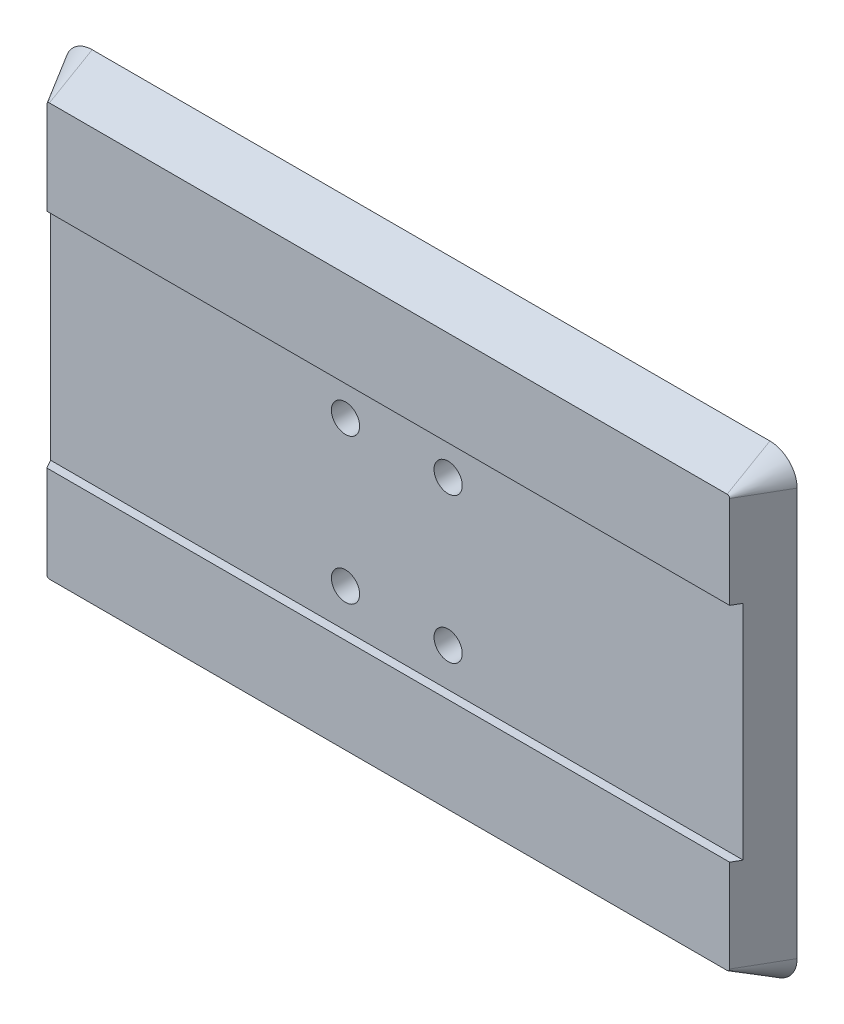
SolidWorks part; units mm, degrees
ref_plane "前视基准面" through (0, 0, 0) normal (0, 0, 1) x (1, 0, 0)
ref_plane "上视基准面" through (0, 0, 0) normal (0, 1, 0) x (1, 0, 0)
ref_plane "右视基准面" through (0, 0, 0) normal (1, 0, 0) x (0, 0, -1)
sketch "草图1" plane through (0, 0, 0) normal (0, 0, 1) x (1, 0, 0)
  line L1 (3.18, 0) -> (82.42, 0)
  line L2 (0, 3.18) -> (0, 50.82)
  line L3 (3.18, 54) -> (82.42, 54)
  line L4 (85.6, 3.18) -> (85.6, 50.82)
  arc A0 (82.42, 0) -> (85.6, 3.18) centre (82.42, 3.18) ccw
  arc A1 (85.6, 50.82) -> (82.42, 54) centre (82.42, 50.82) ccw
  arc A2 (3.18, 0) -> (0, 3.18) centre (3.18, 3.18) cw
  arc A3 (0, 50.82) -> (3.18, 54) centre (3.18, 50.82) cw
  point P7 (85.6, 0)
  point P10 (85.6, 54)
  point P13 (0, 0)
  point P16 (0, 54)
  dimension "D3" = 3.18
  dimension "D1" = 85.6
  dimension "D2" = 54
extrude "凸台-拉伸1" add sketch "草图1" along normal blind 5
chamfer "倒角2" distance 5 angle 30 8 edges at (85.6, 27, 5) (84.6686, 53.0686, 5) (84.6686, 0.9314, 5) (42.8, 54, 5) (42.8, 0, 5) (0.9314, 53.0686, 5) (0.9314, 0.9314, 5) (0, 27, 5) first distance on face at (85.6, 27, 2.5) first distance on face at (84.3393, 52.7393, 2.5) first distance on face at (84.3393, 1.2607, 2.5) first distance on face at (42.8, 54, 2.5) first distance on face at (42.8, 0, 2.5) first distance on face at (1.2607, 52.7393, 2.5) first distance on face at (1.2607, 1.2607, 2.5) first distance on face at (0, 27, 2.5)
sketch "草图5" plane through (0, 0, 5) normal (0, 0, 1) x (1, 0, 0)
  line L0 (2.8868, 27) -> (82.7132, 27) construction
  line L1 (2.8868, 50.82) -> (2.8868, 3.18) construction
  line L2 (82.7132, 3.18) -> (82.7132, 50.82) construction
  line L3 (82.7132, 27) -> (42.8, 27) construction
  line L5 (2.8868, 40) -> (95.1935, 40)
  line L6 (2.8868, 40) -> (2.8868, 14)
  line L7 (2.8868, 14) -> (95.1935, 14)
  line L8 (95.1935, 40) -> (95.1935, 14)
  dimension "D1" = 26
extrude "切除-拉伸2" cut sketch "草图5" against normal blind 1
sketch "草图6" plane through (2.8868, 0, 0) normal (1, 0, 0) x (0, 0, -1)
  line L1 (-5, 14) -> (-4, 14)
  line L2 (-5, 14) -> (-5, 40)
  line L3 (-5, 40) -> (-4, 40)
  line L4 (-4, 14) -> (-4, 40)
extrude "切除-拉伸3" cut sketch "草图6" against normal blind 5
hole_wizard "M4 螺纹孔3" positions "草图9" profile "草图10" tap size "M4" standard "ISO"
sketch "草图9" plane through (0, 0, 4) normal (0, 0, 1) x (1, 0, 0)
  line L0 (42.8, 14) -> (42.8, 40) construction
  line L1 (2.3094, 14) -> (83.2906, 14) construction
  line L2 (83.2906, 40) -> (2.3094, 40) construction
  line L3 (42.8, 40) -> (42.8, 27) construction
  line L4 (42.8, 27) -> (86.3075, 27) construction
  point P0 (48.8, 18.5)
  point P15 (48.8, 35.5)
  point P16 (36.8, 18.5)
  point P17 (36.8, 35.5)
  dimension "D1" = 12
  dimension "D2" = 17
sketch "草图10" plane through (48.8, 18.5, 4) normal (1, 0, 0) x (0, -1, 0)
  line L0 (0, 0) -> (0, 11.0914)
  line L1 (0, 11.0914) -> (1.65, 10.1)
  line L2 (1.65, 10.1) -> (1.65, 0)
  line L5 (1.65, 0) -> (0, 0)
  line L10 (0, 11.0914) -> (-1.65, 10.1) construction
  line L11 (0, -6.35) -> (0, 107.95) construction
  dimension "螺纹孔钻头直径" = 3.3
  dimension "螺纹孔钻头深度" = 10.1
  dimension "导头角度" = 118
cosmetic thread "孔螺蚊线7" parameters "D1"=4, "D2"=4
cosmetic thread "孔螺蚊线8" parameters "D1"=4, "D2"=4
cosmetic thread "孔螺蚊线9" parameters "D1"=4, "D2"=4
cosmetic thread "孔螺蚊线10" parameters "D1"=4, "D2"=4
